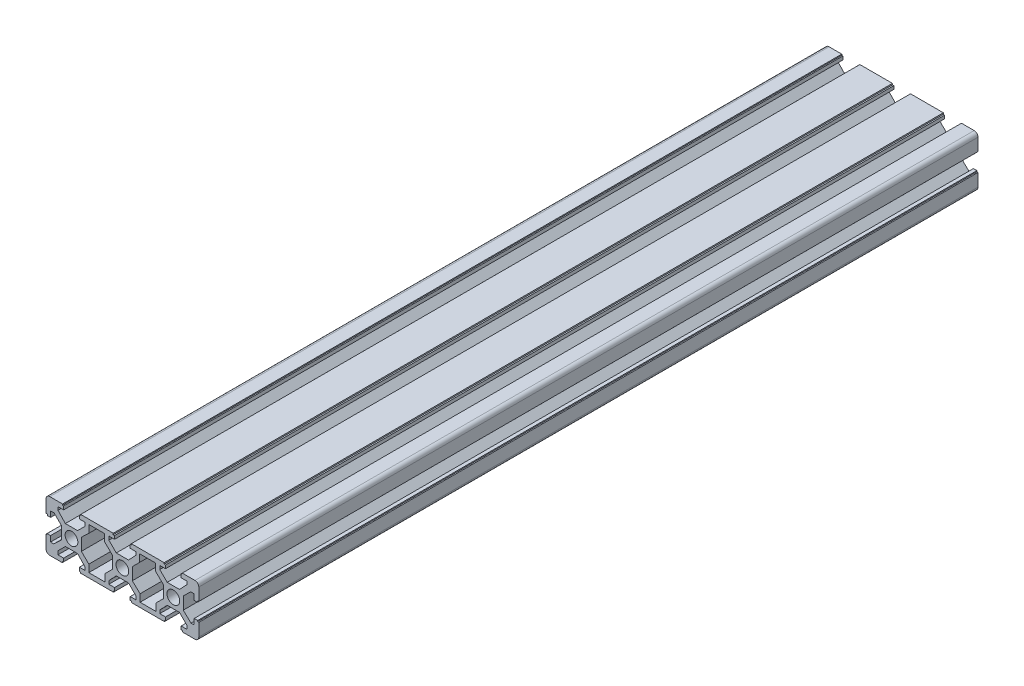
SolidWorks part; units mm, degrees
ref_plane "Front Plane" through (0, 0, 0) normal (0, 0, 1) x (1, 0, 0)
ref_plane "Top Plane" through (0, 0, 0) normal (0, 1, 0) x (1, 0, 0)
ref_plane "Right Plane" through (0, 0, 0) normal (1, 0, 0) x (0, 0, -1)
sketch "Sketch1" plane through (0, 0, 0) normal (0, 0, 1) x (1, 0, 0)
  line L0 (-13.0596, 5.3047) -> (-13.0596, 8.2)
  line L1 (-13.0596, 8.2) -> (-6.9404, 8.2)
  line L2 (6.8, 5.3047) -> (6.8, 8.2)
  line L3 (-6.9404, 5.3047) -> (-6.9404, 8.2)
  line L4 (-11.5, 10) -> (-8.5, 10)
  line L5 (-30, -3.4975) -> (-30, -10)
  line L6 (-28.5, -10) -> (-23.6, -10)
  line L7 (-16.1, 2.4047) -> (-13.0596, 5.3047)
  line L8 (-10, -3.6) -> (-10, 3.4975) construction
  line L9 (-8.3975, -10) -> (8.5, -10) construction
  line L10 (-13.2, -5.3047) -> (-13.2, -8.2)
  line L11 (-13.2, -8.2) -> (-6.8, -8.2)
  line L12 (-6.8, -5.3047) -> (-6.8, -8.2)
  line L13 (-16.1, -2.4047) -> (-13.2, -5.3047)
  line L14 (-16.1, -2.4047) -> (-16.1, 2.4047)
  line L15 (-16.5025, -9.5731) -> (-16.5025, -10)
  line L16 (-16.925, -9.5658) -> (-16.5025, -9.5731)
  line L17 (-16.925, -8.2) -> (-16.925, -9.5658)
  line L18 (-14.6953, -8.2) -> (-16.925, -8.2)
  line L19 (-14.6953, -8.2) -> (-14.6953, -6.9404)
  line L20 (-16.5025, -10) -> (-11.6025, -10)
  line L21 (-8.3975, -10) -> (-11.6025, -10)
  line L22 (-17.5953, -3.9) -> (-14.6953, -6.9404)
  line L23 (-23.6, -9.4791) -> (-23.6, -10)
  line L24 (-23.075, -9.4791) -> (-23.6, -9.4791)
  line L25 (-23.075, -8.2) -> (-23.075, -9.4791)
  line L26 (-25.3047, -8.2) -> (-23.075, -8.2)
  line L27 (-25.3047, -8.2) -> (-25.3047, -6.8)
  line L28 (-22.4047, -3.9) -> (-25.3047, -6.8)
  line L29 (-22.4047, -3.9) -> (-17.5953, -3.9)
  line L30 (-29.5731, -3.4975) -> (-30, -3.4975)
  line L31 (-29.5658, -3.075) -> (-29.5731, -3.4975)
  line L32 (-28.2, -3.075) -> (-29.5658, -3.075)
  line L33 (-28.2, -5.3047) -> (-28.2, -3.075)
  line L34 (-28.2, -5.3047) -> (-26.9404, -5.3047)
  line L35 (10, 8.2) -> (13.0596, 8.2)
  line L36 (-11.5, 10) -> (-16.4, 10)
  line L37 (-23.9, -2.4047) -> (-26.9404, -5.3047)
  line L38 (-29.4791, 3.6) -> (-30, 3.6)
  line L39 (-29.4791, 3.075) -> (-29.4791, 3.6)
  line L40 (-28.2, 3.075) -> (-29.4791, 3.075)
  line L41 (-28.2, 5.3047) -> (-28.2, 3.075)
  line L42 (-28.2, 5.3047) -> (-26.8, 5.3047)
  line L43 (-23.9, 2.4047) -> (-26.8, 5.3047)
  line L44 (-23.9, 2.4047) -> (-23.9, -2.4047)
  line L45 (-22.4047, 3.9) -> (-25.3047, 6.9404)
  line L46 (3, 4.9) -> (-3, 6.4) construction
  line L47 (-25.3047, 8.2) -> (-25.3047, 6.9404)
  line L48 (-17.5953, 3.9) -> (-14.6953, 6.8)
  line L49 (-14.6953, 8.2) -> (-14.6953, 6.8)
  line L50 (-30, 3.6) -> (-30, 10)
  line L51 (-23.4975, 10) -> (-30, 10)
  line L52 (-28.5, -10) -> (-11.6025, -10) construction
  line L54 (30, 8.5035) -> (30, 10) construction
  line L55 (13.0596, 5.3047) -> (13.0596, 8.2)
  line L56 (-30, -10) -> (-10, 10) construction
  line L57 (-30, 10) -> (-10, -10) construction
  line L58 (3, 6.4) -> (-3, 4.9) construction
  line L59 (-3, 6.4) -> (-3, 4.9) construction
  line L60 (0, 0) -> (0, -3.9) construction
  line L61 (-20, 0) -> (-23.9, 0) construction
  line L62 (-20, 0) -> (-20, 3.9) construction
  line L63 (-20, 0) -> (-16.1, 0) construction
  line L64 (-23, 6.4) -> (-17, 6.4) construction
  line L65 (-23, 6.4) -> (-23, 4.9) construction
  line L66 (-23, 4.9) -> (-17, 4.9) construction
  line L67 (-16.4, 9.4791) -> (-16.4, 10)
  line L68 (-16.925, 9.4791) -> (-16.4, 9.4791)
  line L69 (-16.925, 8.2) -> (-16.925, 9.4791)
  line L70 (-20, 0) -> (-20, -3.9) construction
  line L71 (-14.6953, 8.2) -> (-16.925, 8.2)
  line L72 (3, 4.9) -> (-3, 4.9) construction
  line L73 (3, 6.4) -> (3, 4.9) construction
  line L74 (3, 6.4) -> (-3, 6.4) construction
  line L75 (0, 0) -> (-3.9, 0) construction
  line L76 (0, 0) -> (0, 3.9) construction
  line L77 (-17, 6.4) -> (-17, 4.9) construction
  line L78 (-23, 6.4) -> (-17, 4.9) construction
  line L79 (-23, 4.9) -> (-17, 6.4) construction
  line L80 (0, 0) -> (3.9, 0) construction
  line L81 (10, 10) -> (-10, -10) construction
  line L82 (10, -10) -> (-10, 10) construction
  line L83 (6.8, 8.2) -> (10, 8.2)
  line L84 (3.4975, 9.5731) -> (3.4975, 10)
  line L85 (3.075, 9.5658) -> (3.4975, 9.5731)
  line L86 (3.075, 8.2) -> (3.075, 9.5658)
  line L87 (-17.5953, 3.9) -> (-22.4047, 3.9)
  line L88 (5.3047, 8.2) -> (3.075, 8.2)
  line L89 (-25.3047, 8.2) -> (-23.075, 8.2)
  line L90 (-23.075, 8.2) -> (-23.075, 9.5658)
  line L91 (-23.075, 9.5658) -> (-23.4975, 9.5731)
  line L92 (-23.4975, 9.5731) -> (-23.4975, 10)
  line L93 (-2.4047, 3.9) -> (2.4047, 3.9)
  line L94 (-5.3047, 8.2) -> (-3.075, 8.2)
  line L95 (-3.075, 8.2) -> (-3.075, 9.4791)
  line L96 (-3.075, 9.4791) -> (-3.6, 9.4791)
  line L97 (-3.6, 9.4791) -> (-3.6, 10)
  line L98 (6.9404, -5.3047) -> (6.9404, -8.2)
  line L99 (3.4975, 10) -> (8.3975, 10)
  line L100 (-5.3047, 8.2) -> (-5.3047, 6.8)
  line L101 (-2.4047, 3.9) -> (-5.3047, 6.8)
  line L102 (5.3047, 8.2) -> (5.3047, 6.9404)
  line L103 (2.4047, 3.9) -> (5.3047, 6.9404)
  line L104 (3.9, 2.4047) -> (3.9, -2.4047)
  line L105 (3.9, 2.4047) -> (6.8, 5.3047)
  line L106 (6.9404, -8.2) -> (10, -8.2)
  line L107 (8.5, -10) -> (11.6025, -10)
  line L108 (8.3975, 10) -> (11.5, 10)
  line L109 (28.5, -10) -> (30, -10)
  line L110 (30, -8.3975) -> (30, -10)
  line L111 (3.9, -2.4047) -> (6.9404, -5.3047)
  line L112 (-8.5, 10) -> (-3.6, 10)
  line L113 (28.3975, 10) -> (30, 10)
  line L114 (30, 8.5035) -> (30, 10)
  line L116 (-30, -3.4975) -> (-30, 3.6) construction
  line L117 (-28.5, -10) -> (-30, -10)
  line L118 (2.4047, -3.9) -> (-2.4047, -3.9)
  line L119 (2.4047, -3.9) -> (5.3047, -6.8)
  line L120 (5.3047, -8.2) -> (5.3047, -6.8)
  line L121 (5.3047, -8.2) -> (3.075, -8.2)
  line L122 (3.075, -8.2) -> (3.075, -9.4791)
  line L123 (3.075, -9.4791) -> (3.6, -9.4791)
  line L124 (3.6, -9.4791) -> (3.6, -10)
  line L125 (-2.4047, -3.9) -> (-5.3047, -6.9404)
  line L126 (-3.4975, -10) -> (-8.3975, -10)
  line L127 (-5.3047, -8.2) -> (-5.3047, -6.9404)
  line L128 (-5.3047, -8.2) -> (-3.075, -8.2)
  line L129 (-3.075, -8.2) -> (-3.075, -9.5658)
  line L130 (-3.075, -9.5658) -> (-3.4975, -9.5731)
  line L131 (-3.4975, -9.5731) -> (-3.4975, -10)
  line L132 (-3.9, -2.4047) -> (-3.9, 2.4047)
  line L133 (-3.9, -2.4047) -> (-6.8, -5.3047)
  line L135 (11.6025, -10) -> (28.5, -10) construction
  line L136 (10, -8.2) -> (13.2, -8.2)
  line L137 (13.2, -5.3047) -> (13.2, -8.2)
  line L138 (-3.9, 2.4047) -> (-6.9404, 5.3047)
  line L139 (8.5, -10) -> (3.6, -10)
  line L142 (23, 4.9) -> (17, 6.4) construction
  line L143 (23, 6.4) -> (17, 4.9) construction
  line L144 (17, 6.4) -> (17, 4.9) construction
  line L145 (20, 0) -> (20, -3.9) construction
  line L156 (23, 4.9) -> (17, 4.9) construction
  line L157 (23, 6.4) -> (23, 4.9) construction
  line L158 (23, 6.4) -> (17, 6.4) construction
  line L159 (20, 0) -> (16.1, 0) construction
  line L160 (20, 0) -> (20, 3.9) construction
  line L161 (20, 0) -> (23.9, 0) construction
  line L162 (30, 10) -> (10, -10) construction
  line L163 (30, -10) -> (10, 10) construction
  line L164 (30, -8.3975) -> (30, 8.5) construction
  line L165 (23.4975, 9.5731) -> (23.4975, 10)
  line L166 (23.075, 9.5658) -> (23.4975, 9.5731)
  line L167 (23.075, 8.2) -> (23.075, 9.5658)
  line L168 (25.3047, 8.2) -> (23.075, 8.2)
  line L169 (17.5954, 3.9) -> (22.4047, 3.9)
  line L170 (14.6954, 8.2) -> (16.925, 8.2)
  line L171 (16.925, 8.2) -> (16.925, 9.4791)
  line L172 (16.925, 9.4791) -> (16.4, 9.4791)
  line L173 (16.4, 9.4791) -> (16.4, 10)
  line L174 (30, 8.5) -> (30, 3.6)
  line L175 (23.4975, 10) -> (28.3975, 10)
  line L176 (14.6954, 8.2) -> (14.6954, 6.8)
  line L177 (17.5954, 3.9) -> (14.6954, 6.8)
  line L178 (25.3047, 8.2) -> (25.3047, 6.9404)
  line L179 (22.4047, 3.9) -> (25.3047, 6.9404)
  line L180 (23.9, 2.4047) -> (23.9, -2.4047)
  line L181 (23.9, 2.4047) -> (26.8, 5.3047)
  line L182 (28.2, 5.3047) -> (26.8, 5.3047)
  line L183 (28.2, 5.3047) -> (28.2, 3.075)
  line L184 (28.2, 3.075) -> (29.4791, 3.075)
  line L185 (29.4791, 3.075) -> (29.4791, 3.6)
  line L186 (29.4791, 3.6) -> (30, 3.6)
  line L187 (23.9, -2.4047) -> (26.9404, -5.3047)
  line L188 (11.5, 10) -> (16.4, 10)
  line L189 (28.2, -5.3047) -> (26.9404, -5.3047)
  line L190 (28.2, -5.3047) -> (28.2, -3.075)
  line L191 (28.2, -3.075) -> (29.5658, -3.075)
  line L192 (29.5658, -3.075) -> (29.5731, -3.4975)
  line L193 (29.5731, -3.4975) -> (30, -3.4975)
  line L194 (22.4047, -3.9) -> (17.5954, -3.9)
  line L195 (22.4047, -3.9) -> (25.3047, -6.8)
  line L196 (25.3047, -8.2) -> (25.3047, -6.8)
  line L197 (25.3047, -8.2) -> (23.075, -8.2)
  line L198 (23.075, -8.2) -> (23.075, -9.4791)
  line L199 (23.075, -9.4791) -> (23.6, -9.4791)
  line L200 (23.6, -9.4791) -> (23.6, -10)
  line L201 (17.5954, -3.9) -> (14.6954, -6.9404)
  line L202 (16.5025, -10) -> (11.6025, -10)
  line L203 (14.6954, -8.2) -> (14.6954, -6.9404)
  line L204 (14.6954, -8.2) -> (16.925, -8.2)
  line L205 (16.925, -8.2) -> (16.925, -9.5658)
  line L206 (16.925, -9.5658) -> (16.5025, -9.5731)
  line L207 (16.5025, -9.5731) -> (16.5025, -10)
  line L208 (16.1, -2.4047) -> (16.1, 2.4047)
  line L209 (16.1, -2.4047) -> (13.2, -5.3047)
  line L210 (16.1, 2.4047) -> (13.0596, 5.3047)
  line L211 (28.5, -10) -> (23.6, -10)
  line L212 (30, -3.4975) -> (30, -8.3975)
  line L213 (10, 10) -> (10, -10) construction
  line L215 (30, 8.5035) -> (30, 8.5)
  circle A0 centre (-20, 0) radius 2.5
  circle A2 centre (20, 0) radius 2.5
  circle A8 centre (0, 0) radius 2.5
  point P59 (-20, 0)
  point P67 (-20, 0)
  dimension "D1" = 6
  dimension "D2" = 1.5
  dimension "D4" = 3.075
  dimension "D5" = 3.075
  dimension "D6" = 3.075
  dimension "D7" = 20
  dimension "D8" = 20
extrude "Boss-Extrude1" add sketch "Sketch1" along normal blind 306
fillet "Fillet1" radius 1.5 4 edges at (-30, -10, 153) (30, -10, 153) (30, 10, 153) (-30, 10, 153)
ref_plane "Plane1" through (20, 0, 0) normal (1, 0, 0) x (0, 0, -1)
ref_plane "Plane2" through (-20, 0, 0) normal (1, 0, 0) x (0, 0, -1)
